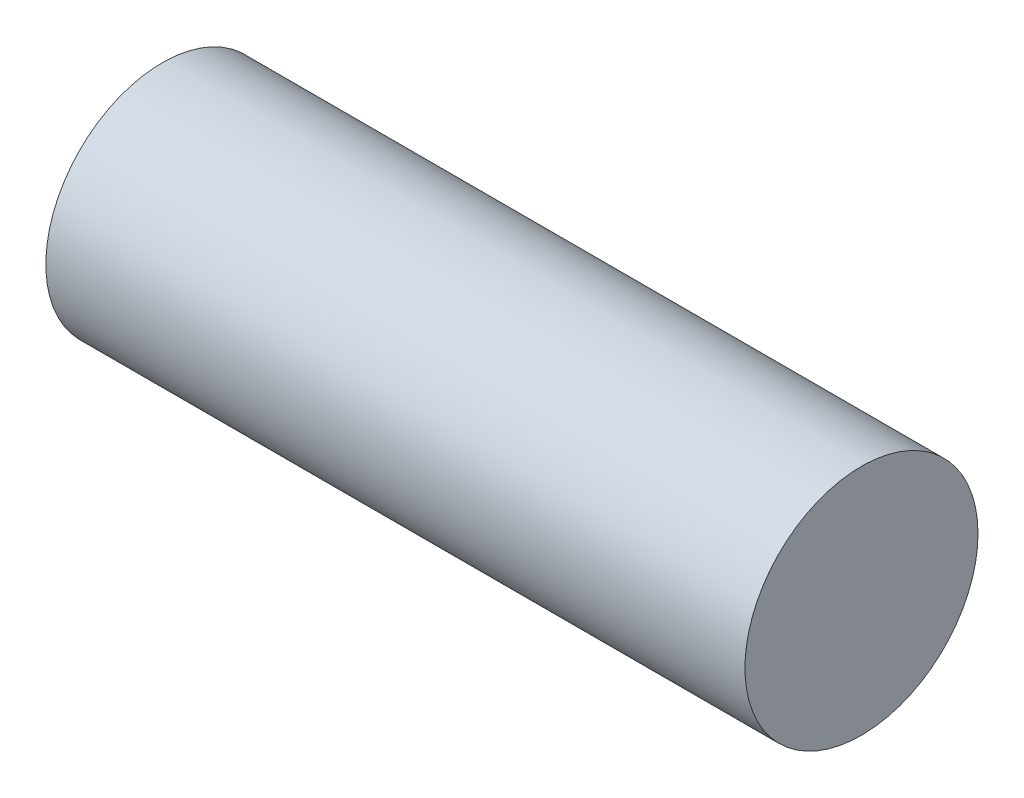
SolidWorks part; units mm, degrees
ref_plane "Front Plane" through (0, 0, 0) normal (0, 0, 1) x (1, 0, 0)
ref_plane "Top Plane" through (0, 0, 0) normal (0, 1, 0) x (1, 0, 0)
ref_plane "Right Plane" through (0, 0, 0) normal (1, 0, 0) x (0, 0, -1)
sketch "Sketch14" plane through (0, 0, 0) normal (1, 0, 0) x (0, 0, -1)
  circle A0 centre (0, 0) radius 0.5
  dimension "D1" = 1
extrude "Boss-Extrude1" add sketch "Sketch14" along normal mid plane 3
ref_axis "Axis1" through (1.5, 0, 0) along (-1, 0, 0)
